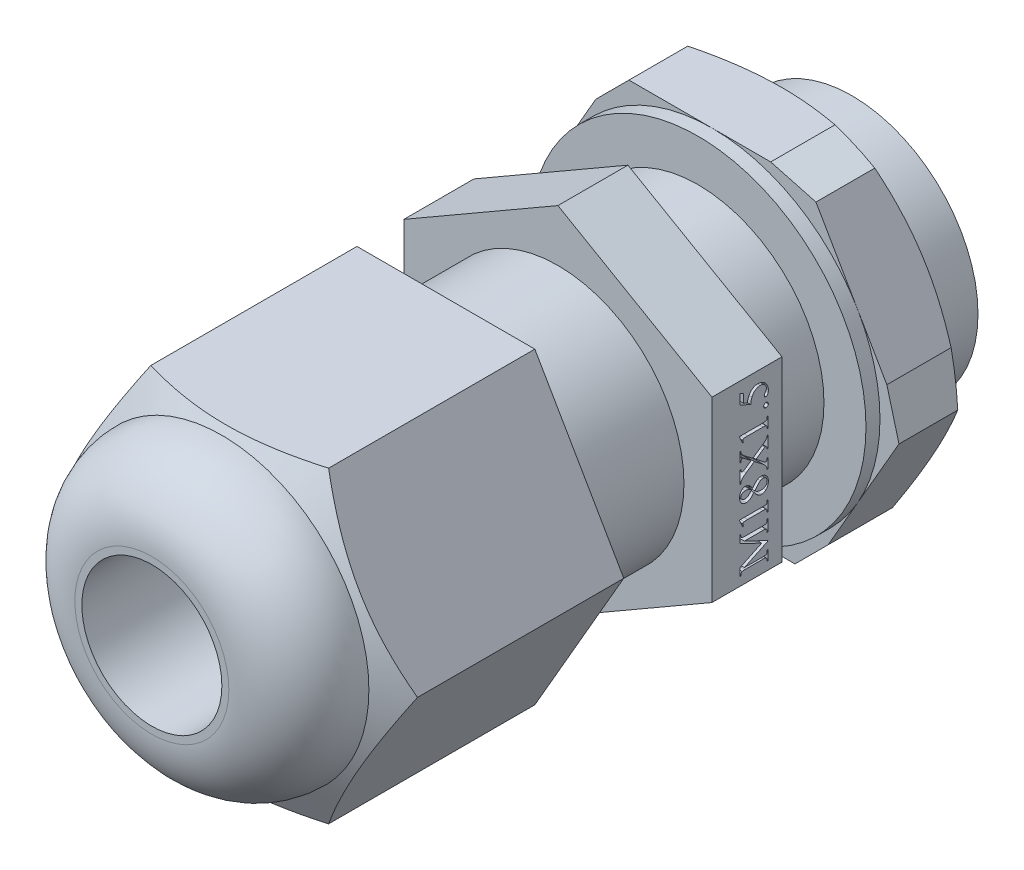
SolidWorks part; units mm, degrees
ref_plane "Front Plane" through (0, 0, 0) normal (0, 0, 1) x (1, 0, 0)
ref_plane "Top Plane" through (0, 0, 0) normal (0, 1, 0) x (1, 0, 0)
ref_plane "Right Plane" through (0, 0, 0) normal (1, 0, 0) x (0, 0, -1)
sketch "Sketch2" plane through (0, 0, 0) normal (0, 0, 1) x (1, 0, 0)
  line L1 (-299.5259, 272.6716) -> (420.4741, 272.6716) construction
sketch "Sketch16" plane through (0, 0, 0) normal (0, 0, 1) x (1, 0, 0)
  circle A0 centre (0, 0) radius 9
  dimension "D1" = 18
extrude "Boss-Extrude1" add sketch "Sketch16" along normal blind 5
sketch "Sketch17" plane through (0, 0, 5) normal (0, 0, 1) x (1, 0, 0)
  line L1 (13.8564, 0) -> (6.9282, 12)
  line L2 (6.9282, 12) -> (-6.9282, 12)
  line L3 (-6.9282, 12) -> (-13.8564, 0)
  line L4 (-13.8564, 0) -> (-6.9282, -12)
  line L5 (-6.9282, -12) -> (6.9282, -12)
  line L6 (6.9282, -12) -> (13.8564, 0)
  circle A0 centre (0, 0) radius 12 construction
  dimension "D1" = 24
extrude "Boss-Extrude2" add sketch "Sketch17" along normal blind 5
sketch "Sketch18" plane through (0, 0, 10) normal (0, 0, 1) x (1, 0, 0)
  circle A0 centre (0, 0) radius 12
  dimension "D1" = 24
extrude "Boss-Extrude3" add sketch "Sketch18" along normal blind 1
sketch "Sketch19" plane through (0, 0, 11) normal (0, 0, 1) x (1, 0, 0)
  circle A0 centre (0, 0) radius 9
  dimension "D1" = 18
extrude "Boss-Extrude4" add sketch "Sketch19" along normal blind 5
sketch "Sketch20" plane through (0, 0, 16) normal (0, 0, 1) x (1, 0, 0)
  line L1 (0, 12.7017) -> (-11, 6.3509)
  line L2 (-11, 6.3509) -> (-11, -6.3509)
  line L3 (-11, -6.3509) -> (0, -12.7017)
  line L4 (0, -12.7017) -> (11, -6.3509)
  line L5 (11, -6.3509) -> (11, 6.3509)
  line L6 (11, 6.3509) -> (0, 12.7017)
  circle A0 centre (0, 0) radius 11 construction
  dimension "D1" = 22
extrude "Boss-Extrude5" add sketch "Sketch20" along normal blind 5
sketch "Sketch21" plane through (0, 0, 21) normal (0, 0, 1) x (1, 0, 0)
  circle A0 centre (0, 0) radius 9
  dimension "D1" = 18
extrude "Boss-Extrude6" add sketch "Sketch21" along normal blind 8
sketch "Sketch22" plane through (0, 0, 29) normal (0, 0, 1) x (1, 0, 0)
  line L1 (-12.7017, 0) -> (-6.3509, -11)
  line L2 (-6.3509, -11) -> (6.3509, -11)
  line L3 (6.3509, -11) -> (12.7017, 0)
  line L4 (12.7017, 0) -> (6.3509, 11)
  line L5 (6.3509, 11) -> (-6.3509, 11)
  line L6 (-6.3509, 11) -> (-12.7017, 0)
  circle A0 centre (0, 0) radius 11 construction
  dimension "D1" = 22
extrude "Boss-Extrude7" add sketch "Sketch22" along normal blind 16
sketch "Sketch24" plane through (0, 0, 45) normal (0, 0, 1) x (1, 0, 0)
  circle A0 centre (0, 0) radius 10.5
  dimension "D1" = 21
extrude "Boss-Extrude8" add sketch "Sketch24" along normal blind 5
sketch "Sketch25" plane through (0, 0, 50) normal (0, 0, 1) x (1, 0, 0)
  circle A0 centre (0, 0) radius 5
  dimension "D1" = 10
extrude "Cut-Extrude1" cut sketch "Sketch25" against normal blind 12
sketch "Sketch26" plane through (0, 0, 0) normal (0, 0, -1) x (-1, 0, 0)
  circle A0 centre (0, 0) radius 6.75
  dimension "D1" = 13.5
extrude "Cut-Extrude2" cut sketch "Sketch26" against normal blind 42
fillet "Fillet1" radius 5 1 edges at (10.5, 0, 50)
sketch "Sketch29" plane through (0, 0, 45) normal (0, 0, 1) x (1, 0, 0)
  circle A0 centre (0, 0) radius 10.5
  circle A1 centre (0, 0) radius 10.5 construction
  circle A2 centre (0, 0) radius 19.2648
extrude "Cut-Extrude6" cut sketch "Sketch29" against normal blind 11 draft 60
sketch "Sketch30" plane through (0, 0, 5) normal (0, 0, -1) x (-1, 0, 0)
  line L0 (-13.8564, 0) -> (-6.9282, 12) construction
  circle A0 centre (0, 0) radius 12
  circle A1 centre (0, 0) radius 18.6783
extrude "Cut-Extrude7" cut sketch "Sketch30" against normal blind 10.7366 draft 60
sketch "Sketch31" plane through (11, 0, 0) normal (1, 0, 0) x (0, 0, -1)
  line L0 (-17, -6.3509) -> (-17, 6.3509) construction
  line L3 (-16, -9) -> (-16, 9) construction
  text T0 "M18X1.5" font "Times New Roman" height 2
  dimension "D1" = 1
extrude "Cut-Extrude8" cut sketch "Sketch31" against normal blind 1
sketch "Sketch32" plane through (-11, 0, 0) normal (-1, 0, 0) x (0, 0, 1)
  line L0 (17, 6.3509) -> (17, -6.3509) construction
  line L1 (21, 6.3509) -> (16, 6.3509) construction
  line L2 (21, -6.3509) -> (16, -6.3509) construction
  line L3 (16, 6.3509) -> (16, -6.3509) construction
  text T0 "СЄ" font "Arial" height 3.5
  dimension "D1" = 1
extrude "Cut-Extrude9" cut sketch "Sketch32" against normal blind 1
chamfer "Chamfer1" distance 1 angle 45 6 edges at (6.9282, -12, 8.0359) (-6.9282, -12, 8.0359) (-13.8564, 0, 8.0359) (-6.9282, 12, 8.0359) (6.9282, 12, 8.0359) (13.8564, 0, 8.0359)
